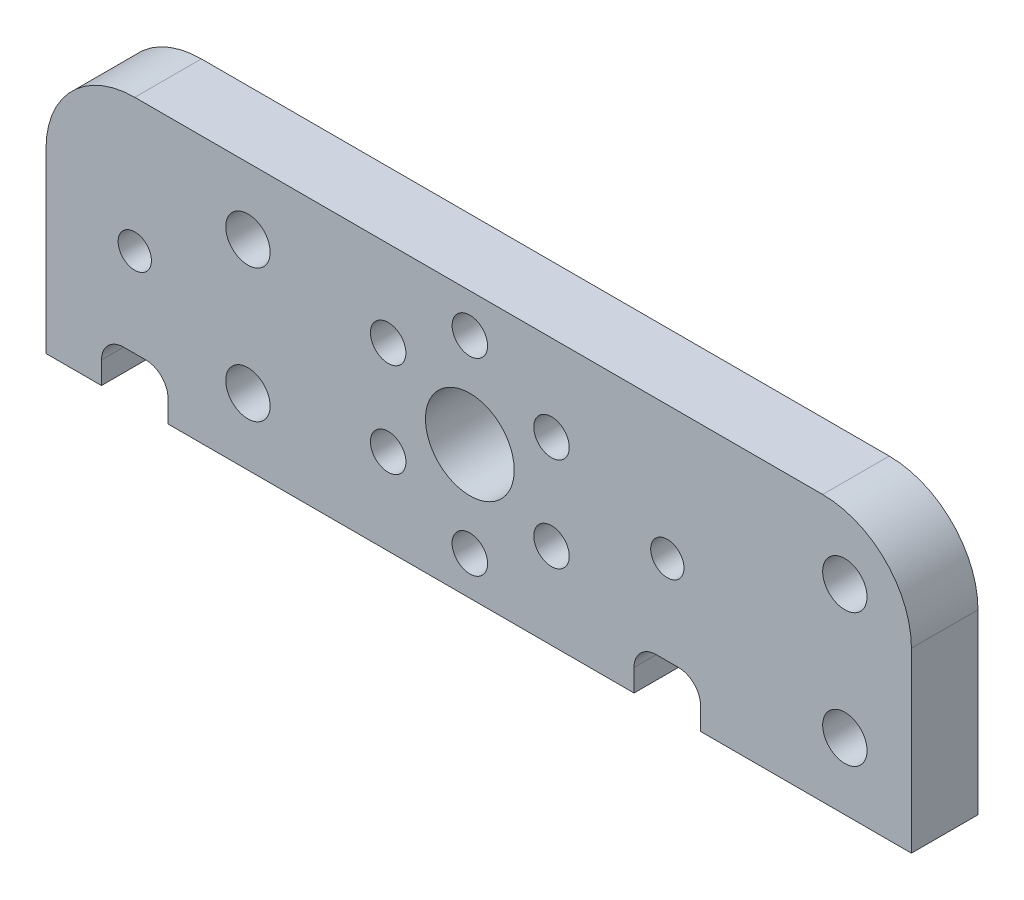
SolidWorks part; units mm, degrees
ref_plane "Front Plane" through (0, 0, 0) normal (0, 0, 1) x (1, 0, 0)
ref_plane "Top Plane" through (0, 0, 0) normal (0, 1, 0) x (1, 0, 0)
ref_plane "Right Plane" through (0, 0, 0) normal (1, 0, 0) x (0, 0, -1)
sketch "Sketch1" plane through (0, 0, 0) normal (0, 0, 1) x (1, 0, 0)
  line L0 (-23.1, 0) -> (15.9, 0) construction
  line L1 (-23.1, -6) -> (15.9, -6)
  line L2 (-23.1, -6) -> (-23.1, 2)
  line L3 (-19.1, 6) -> (11.9, 6)
  line L4 (15.9, -6) -> (15.9, 2)
  line L5 (12.9, -6) -> (12.9, 6.9573) construction
  line L6 (-14, -6) -> (-14, 8.3224) construction
  line L7 (-23.1, -3) -> (15.9, -3) construction
  line L8 (-22.973, 3) -> (15.773, 3) construction
  line L11 (3.4, -6) -> (3.4, -5)
  line L12 (4.4, -4) -> (5.4, -4)
  line L13 (6.4, -6) -> (6.4, -5)
  line L14 (4.9, -6) -> (6.4, -4) construction
  line L15 (3.4, -4) -> (4.9, -6) construction
  line L17 (-20.6, -6) -> (-20.6, -5)
  line L18 (-19.6, -4) -> (-18.6, -4)
  line L19 (-17.6, -6) -> (-17.6, -5)
  line L20 (-19.1, -6) -> (-17.6, -4) construction
  line L21 (-20.6, -4) -> (-19.1, -6) construction
  circle A0 centre (-4, 0) radius 2
  circle A1 centre (4.9, 0) radius 0.75
  arc A2 (11.9, 6) -> (15.9, 2) centre (11.9, 2) cw
  arc A3 (-23.1, 2) -> (-19.1, 6) centre (-19.1, 2) cw
  circle A4 centre (-19.1, 0) radius 0.75
  circle A5 centre (12.9, 3) radius 1
  circle A6 centre (12.9, -3) radius 1
  circle A7 centre (-14, -3) radius 1
  circle A8 centre (-14, 3) radius 1
  arc A9 (5.4, -4) -> (6.4, -5) centre (5.4, -5) cw
  arc A10 (3.4, -5) -> (4.4, -4) centre (4.4, -5) cw
  arc A11 (-18.6, -4) -> (-17.6, -5) centre (-18.6, -5) cw
  arc A12 (-20.6, -5) -> (-19.6, -4) centre (-19.6, -5) cw
  point P0 (0, 0)
  point P34 (4.9, -6)
  point P36 (-19.1, -4)
  point P38 (0, 0)
  point P39 (-19.1, -6)
  point P48 (0, 0)
  point P49 (4.9, -4)
  dimension "D1" = 8.9
  dimension "D2" = 1.5
  dimension "D3" = 4
  dimension "D6" = 4
  dimension "D7" = 4
  dimension "D8" = 11
  dimension "D4" = 24
  dimension "D5" = 4
  dimension "D11" = 1.5
  dimension "D16" = 2
  dimension "D17" = 2
  dimension "D18" = 2
  dimension "D19" = 2
  dimension "D23" = 1
  dimension "D9" = 12
  dimension "D10" = 6
  dimension "D12" = 10
  dimension "D13" = 3
  dimension "D14" = 3
  dimension "D15" = 3
  dimension "D20" = 3
  dimension "D21" = 2
  dimension "D22" = 3
extrude "Boss-Extrude1" add sketch "Sketch1" along normal blind 3 contours L17 A12 L18 A11 L19 L1 L11 A10 L12 A9 L13 L4 A2 L3 A3 L2 A8 A7 A6 A5 A4 A1 A0 region at (-22.692, -2, 0)
sketch "Sketch2" plane through (0, 0, 0) normal (0, 0, 1) x (1, 0, 0)
  circle A0 centre (4.9, 0) radius 0.75
  circle A1 centre (4.9, 0) radius 2.75
  dimension "D1" = 2
extrude "Boss-Extrude2" [suppressed] add sketch "Sketch2" along normal blind 1
sketch "Sketch3" plane through (0, 0, 3) normal (0, 0, 1) x (1, 0, 0)
  circle A0 centre (-4, 0) radius 4.25
  circle A1 centre (-4, 4.25) radius 0.8
  dimension "D1" = 8.5
  dimension "D2" = 1.6
extrude "Cut-Extrude1" cut sketch "Sketch3" against normal blind 3 contours A0 A1 | A0 A1 region at (-4, 3.8973, 3) region at (-4, 4.5756, 3)
pattern_circular "CirPattern1" count 6 over 360 about axis through (-4, 0, 3) along (0, 0, 1) of "Cut-Extrude1"
